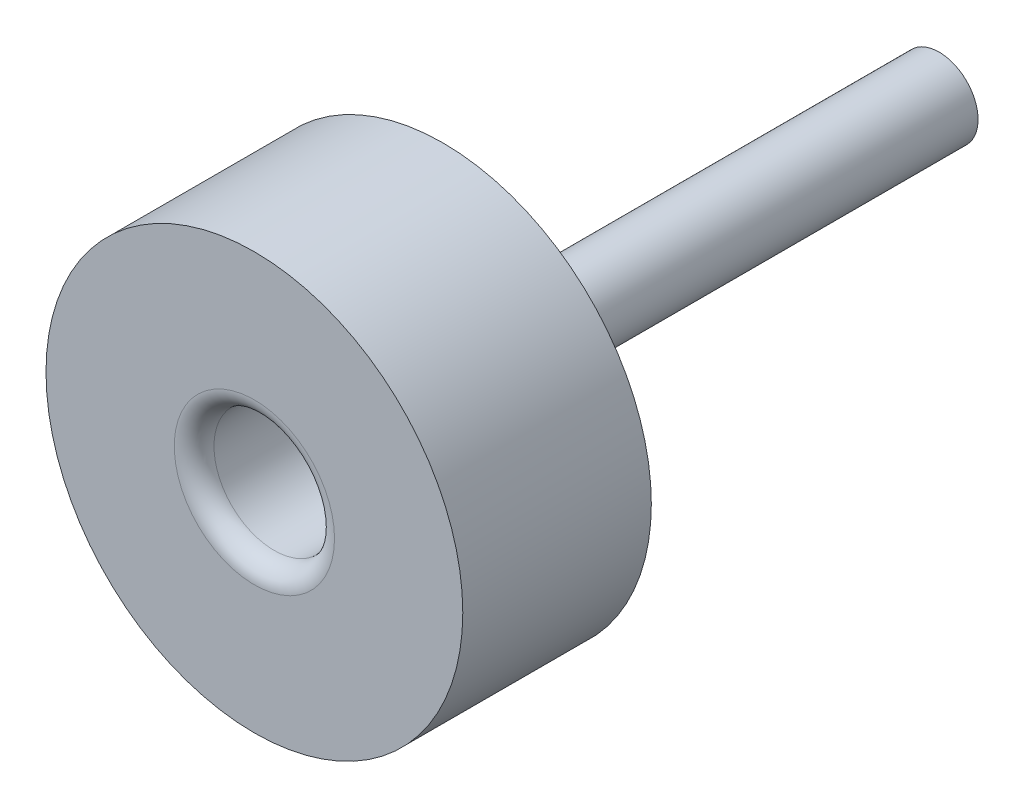
SolidWorks part; units mm, degrees
ref_plane "Ebene vorne" through (0, 0, 0) normal (0, 0, 1) x (1, 0, 0)
ref_plane "Ebene oben" through (0, 0, 0) normal (0, 1, 0) x (1, 0, 0)
ref_plane "Ebene rechts" through (0, 0, 0) normal (1, 0, 0) x (0, 0, -1)
sketch "Skizze1" plane through (0, 0, 0) normal (0, 0, 1) x (1, 0, 0)
  circle A0 centre (0, 0) radius 6
  dimension "D1" = 12
extrude "Aufsatz-Linear austragen1" add sketch "Skizze1" along normal blind 9
sketch "Skizze2" plane through (0, 0, 0) normal (0, 0, -1) x (-1, 0, 0)
  circle A0 centre (0, 0) radius 3.925
  dimension "D1" = 7.85
extrude "Aufsatz-Linear austragen2" add sketch "Skizze2" along normal blind 41
sketch "Skizze3" plane through (0, 0, 9) normal (0, 0, 1) x (1, 0, 0)
  circle A0 centre (0, 0) radius 21
  dimension "D1" = 42
extrude "Aufsatz-Linear austragen3" add sketch "Skizze3" along normal blind 19
sketch "Skizze4" plane through (0, 0, 28) normal (0, 0, 1) x (1, 0, 0)
  circle A0 centre (0, 0) radius 6.075
  dimension "D1" = 12.15
extrude "Schnitt-Linear austragen2" cut sketch "Skizze4" against normal blind 10
fillet "Verrundung1" radius 2 1 edges at (6.075, 0, 28)
sketch "Skizze5" plane through (0, 0, -41) normal (0, 0, -1) x (-1, 0, 0)
  circle A0 centre (0, 0) radius 3.425
  dimension "D1" = 6.85
